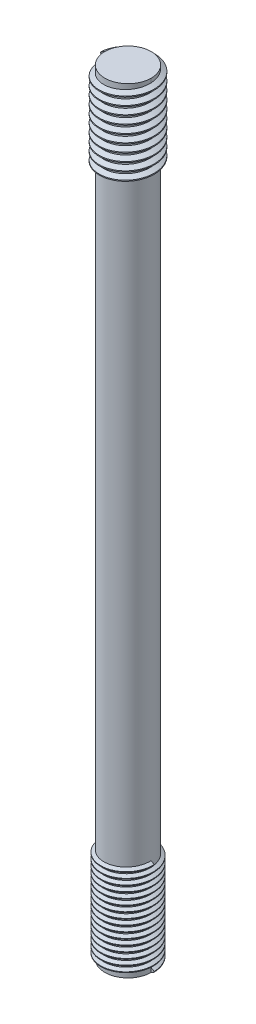
SolidWorks part; units mm, degrees
ref_plane "Front Plane" through (0, 0, 0) normal (0, 0, 1) x (1, 0, 0)
ref_plane "Top Plane" through (0, 0, 0) normal (0, 1, 0) x (1, 0, 0)
ref_plane "Right Plane" through (0, 0, 0) normal (1, 0, 0) x (0, 0, -1)
sketch "Sketch1" plane through (0, 0, 0) normal (0, 1, 0) x (1, 0, 0)
  circle A0 centre (0, 0) radius 2
  dimension "D1" = 4
extrude "Boss-Extrude1" add sketch "Sketch1" along normal blind 67
thread "Thread1" pitch 0.7 method extrude profile "Thread Profile1" start angle 0, offset 0, length 7, pitch 0.7, diameter 4
ref_plane "Plane1" through (-2, 67, 0) normal (0, 0, 1) x (-1, 0, 0)
sketch "Thread Profile1" plane through (-2, 67, 0) normal (0, 0, 1) x (-1, 0, 0)
  line L0 (0, 0) -> (0, 0.7) construction
  line L1 (0, 0) -> (0.3789, 0.2187)
  line L2 (0.3789, 0.2187) -> (0.3789, 0.3062)
  line L3 (0.3789, 0.3062) -> (0, 0.525)
  line L4 (0.3789, 0.2625) -> (0, 0.2625) construction
  line L11 (0, 0) -> (0, 0.525)
  point P2 (0, 0)
  dimension "Pitch" = 0.7
  dimension "Profile_Angle" = 60
  dimension "Profile_Land" = 0.0875
  dimension "Profile_Height" = 0.3789
thread "Thread2" pitch 0.5 method extrude profile "Thread Profile2" start angle 0, offset 0, length 8, pitch 0.5, diameter 4
ref_plane "Plane2" through (2, 0, 0) normal (0, 0, 1) x (1, 0, 0)
sketch "Thread Profile2" plane through (2, 0, 0) normal (0, 0, 1) x (1, 0, 0)
  line L0 (0, 0) -> (0, 0.5) construction
  line L1 (0, 0) -> (0.2706, 0.1562)
  line L2 (0.2706, 0.1562) -> (0.2706, 0.2187)
  line L3 (0.2706, 0.2187) -> (0, 0.375)
  line L4 (0.2706, 0.1875) -> (0, 0.1875) construction
  line L11 (0, 0) -> (0, 0.375)
  point P2 (0, 0)
  dimension "Pitch" = 0.5
  dimension "Profile_Angle" = 60
  dimension "Profile_Land" = 0.0625
  dimension "Profile_Height" = 0.2706
